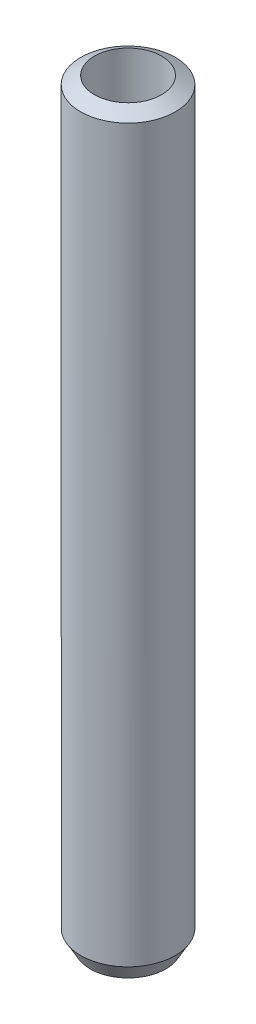
SolidWorks part; units mm, degrees
ref_plane "Front Plane" through (0, 0, 0) normal (0, 0, 1) x (1, 0, 0)
ref_plane "Top Plane" through (0, 0, 0) normal (0, 1, 0) x (1, 0, 0)
ref_plane "Right Plane" through (0, 0, 0) normal (1, 0, 0) x (0, 0, -1)
sketch "Sketch1" plane through (0, 0, 0) normal (0, 1, 0) x (1, 0, 0)
  circle A0 centre (0, 0) radius 17.5
  dimension "SHAFT_OD" = 35
extrude "Boss-Extrude1" add sketch "Sketch1" along normal blind 279.9823
sketch "Sketch2" plane through (0, 0, 0) normal (0, 1, 0) x (1, 0, 0)
  circle A0 centre (0, 0) radius 12.4151
  dimension "BORE_D" = 24.8301
extrude "Cut-Extrude1" cut sketch "Sketch2" along normal through all
chamfer "Chamfer1" distance 3.4903 angle 60 2 edges at (0, 279.9823, 17.5) (0, 0, 17.5) first distance on face at (0, 279.9823, 17.5) first distance on face at (0, 0, 12.4151)
